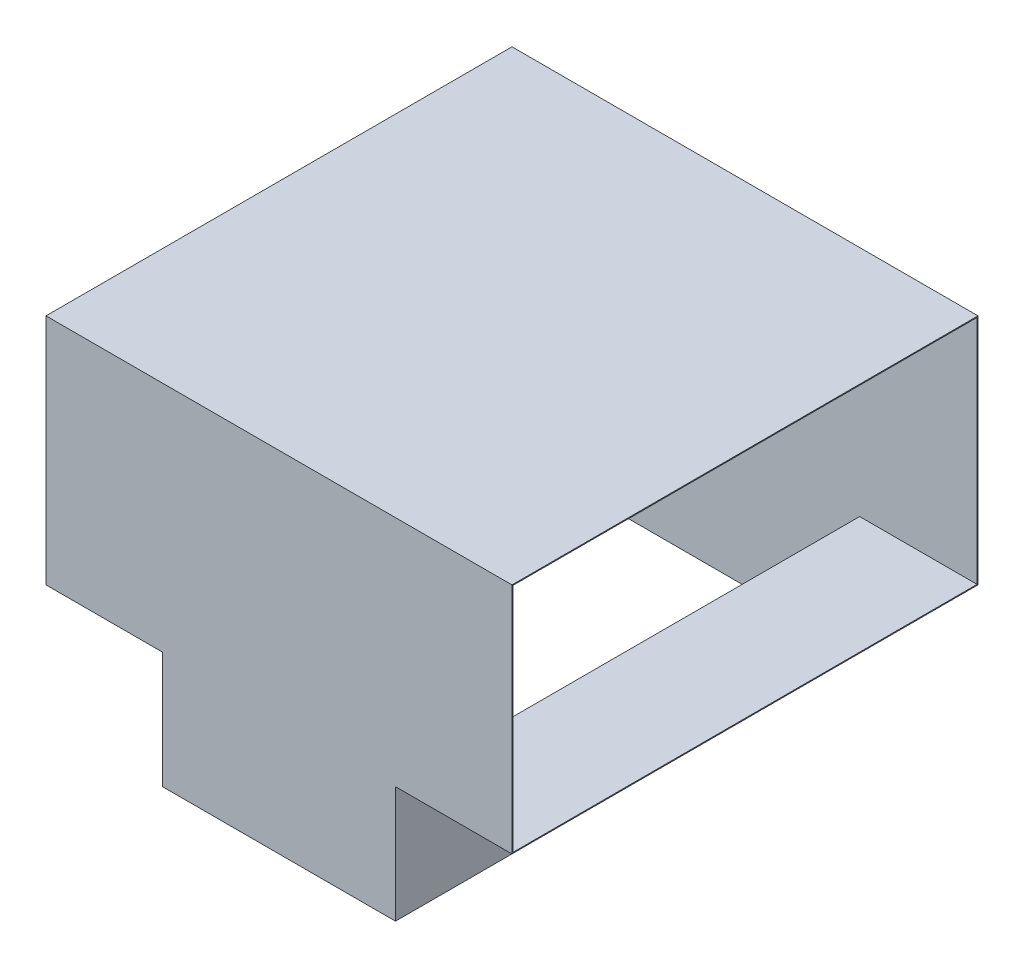
SolidWorks part; units mm, degrees
material "Plain Carbon Steel"
ref_plane "Front Plane" through (0, 0, 0) normal (0, 0, 1) x (1, 0, 0)
ref_plane "Top Plane" through (0, 0, 0) normal (0, 1, 0) x (1, 0, 0)
ref_plane "Right Plane" through (0, 0, 0) normal (1, 0, 0) x (0, 0, -1)
sketch "Sketch1" plane through (0, 0, 0) normal (1, 0, 0) x (0, 0, -1)
  line L0 (-500, 250) -> (500, -250) construction
  line L1 (-500, 250) -> (500, 250)
  line L2 (-500, 250) -> (-500, -250)
  line L3 (-500, -250) -> (500, -250)
  line L4 (500, 250) -> (500, -250)
  dimension "Width" = 1000
  dimension "Height" = 500
extrude "Extrude-Thin1" add sketch "Sketch1" along normal mid plane 1000 thin thin type one direction reverse wall 2
sketch "Sketch2" plane through (0, -250, 0) normal (0, -1, 0) x (1, 0, 0)
  line L1 (-250, 500) -> (250, 500)
  line L2 (-250, 500) -> (-250, -500)
  line L3 (-250, -500) -> (250, -500)
  line L4 (250, 500) -> (250, -500)
  line L6 (-250, 500) -> (250, -500) construction
  dimension "Height" = 500
  dimension "Width" = 1000
extrude "Extrude-Thin2" add sketch "Sketch2" along normal blind 250 thin thin type one direction reverse wall 2
sketch "Sketch3" plane through (0, -500, 0) normal (0, -1, 0) x (1, 0, 0)
  line L0 (-248, 498) -> (-248, -498) construction
  line L1 (248, 498) -> (-248, 498) construction
  line L2 (248, -498) -> (248, 498) construction
  line L3 (-248, -498) -> (248, -498) construction
  line L4 (-248, 498) -> (-248, -498)
  line L5 (248, 498) -> (-248, 498)
  line L6 (248, -498) -> (248, 498)
  line L7 (-248, -498) -> (248, -498)
extrude "Cut-Extrude1" cut sketch "Sketch3" against normal up to next
sketch "Sketch4" plane through (0, 0, 0) normal (0, 0, 1) x (1, 0, 0)
  line L0 (500, -248) -> (500, 248) construction
  line L1 (-500, -248) -> (-500, 248) construction
  line L2 (250, -500) -> (-250, -500) construction
  point P0 (500, 0)
  point P1 (0, 0)
  point P2 (-500, 0)
  point P4 (0, -500)
other "CPoint1" parameters "Diameter"=564.1896, "StubLength"=500
ref_axis "Axis1" through (510, 0, 0) along (-1, 0, 0)
other "CPoint2" parameters "Diameter"=564.1896, "StubLength"=500
ref_axis "Axis2" through (-510, 0, 0) along (1, 0, 0)
other "CPoint3" parameters "Diameter"=564.1896, "StubLength"=500
ref_axis "Axis3" through (0, -510, 0) along (0, 1, 0)
other "RPoint1"
